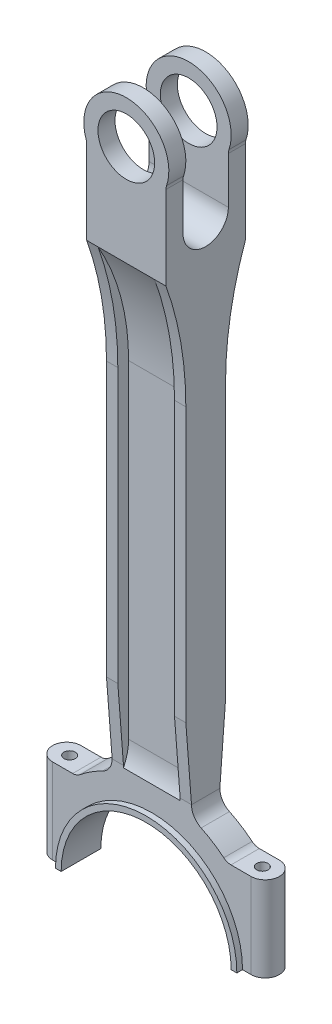
SolidWorks part; units mm, degrees
ref_plane "Front Plane" through (0, 0, 0) normal (0, 0, 1) x (1, 0, 0)
ref_plane "Top Plane" through (0, 0, 0) normal (0, 1, 0) x (1, 0, 0)
ref_plane "Right Plane" through (0, 0, 0) normal (1, 0, 0) x (0, 0, -1)
sketch "Sketch1" plane through (0, 0, 0) normal (0, 0, 1) x (1, 0, 0)
  line L0 (7, 27.7281) -> (7, -70.8443)
  line L1 (-7, 27.7281) -> (-7, -70.8443)
  line L2 (-20, -89.5793) -> (-15, -89.5793)
  line L3 (15, -89.5793) -> (20, -89.5793)
  line L4 (-20, -89.5793) -> (-20, -74.5793)
  line L5 (-20, -74.5793) -> (-13.9642, -74.5793)
  line L6 (13.9642, -74.5793) -> (20, -74.5793)
  line L7 (20, -74.5793) -> (20, -89.5793)
  circle A0 centre (0, 30.4207) radius 5
  arc A1 (7, 27.7281) -> (-7, 27.7281) centre (0, 30.4207) ccw
  arc A2 (-7, -70.8443) -> (-12.6948, -74.1248) centre (0, -89.5793) ccw
  arc A3 (15, -89.5793) -> (-15, -89.5793) centre (0, -89.5793) ccw
  arc A4 (12.6948, -74.1248) -> (7, -70.8443) centre (0, -89.5793) ccw
  arc A5 (-13.9642, -74.5793) -> (-12.6948, -74.1248) centre (-13.9642, -72.5793) ccw
  arc A6 (13.9642, -74.5793) -> (12.6948, -74.1248) centre (13.9642, -72.5793) cw
  point P18 (-13.2288, -74.5793)
  dimension "D1" = 10
  dimension "D2" = 15
  dimension "D4" = 30
  dimension "D5" = 40
  dimension "D9" = 2
  dimension "D3" = 120
  dimension "D6" = 7.5
  dimension "D7" = 7
  dimension "D8" = 7
  dimension "D10" = 5
extrude "Boss-Extrude1" add sketch "Sketch1" along normal blind 14
sketch "Sketch2" plane through (7, 0, 0) normal (1, 0, 0) x (0, 0, -1)
  line L0 (-11, 19.1557) -> (-11, 94.0269)
  line L2 (-11, 94.0269) -> (-3, 94.0269)
  line L3 (-3, 19.1557) -> (-3, 94.0269)
  line L4 (-14, -70.8443) -> (-14, 27.7281) construction
  arc A0 (-11, 19.1557) -> (-3, 19.1557) centre (-7, 19.1557) ccw
  dimension "D1" = 8
  dimension "D2" = 3
  dimension "D3" = 90
extrude "Cut-Extrude1" cut sketch "Sketch2" against normal blind 21 and the other way blind 14
sketch "Sketch3" plane through (-7, 0, 0) normal (-1, 0, 0) x (0, 0, 1)
  line L0 (14, 27.7281) -> (14, -70.8443) construction
  line L1 (0, 27.7281) -> (0, -70.8443) construction
  line L2 (3.5, -7.5793) -> (3.5, -89.5793)
  line L3 (14, -89.5793) -> (0, -89.5793) construction
  line L4 (10.5, -7.5793) -> (10.5, -89.5793)
  line L5 (0, 12.6135) -> (0, -89.5793)
  line L6 (14, 12.6135) -> (14, -89.5793)
  line L7 (14, -89.5793) -> (10.5, -89.5793)
  line L8 (0, -89.5793) -> (3.5, -89.5793)
  arc A0 (14, 12.6135) -> (10.5, -7.5793) centre (70.5, -7.5793) ccw
  arc A1 (0, 12.6135) -> (3.5, -7.5793) centre (-56.5, -7.5793) cw
  dimension "D1" = 60
  dimension "D2" = 60
  dimension "D3" = 82
  dimension "D4" = 60
  dimension "D5" = 3.5
  dimension "D6" = 3.5
  dimension "D7" = 82
extrude "Cut-Extrude2" cut sketch "Sketch3" against normal blind 28 and the other way blind 26
sketch "Sketch4" plane through (0, 0, 0) normal (1, 0, 0) x (0, 0, -1)
  line L0 (-5.4, -7.4574) -> (-5.4, -65.3135)
  line L1 (-3.5, -70.8443) -> (19.6376, -70.8443)
  line L2 (19.6376, -70.8443) -> (19.6376, 12.6135)
  line L3 (19.6376, 12.6135) -> (0, 12.6135)
  line L4 (-8.6, -7.4574) -> (-8.6, -65.3135)
  line L9 (-14, 12.6135) -> (-24.5306, 12.6135)
  line L10 (-24.5306, 12.6135) -> (-24.5306, -70.8443)
  line L12 (-24.5306, -70.8443) -> (-10.5, -70.8443)
  arc A0 (0, 12.6135) -> (-5.4, -7.4574) centre (34.6, -7.4574) ccw
  arc A1 (-5.4, -65.3135) -> (-3.5, -70.8443) centre (3.6, -65.3135) ccw
  arc A2 (-8.6, -7.4574) -> (-14, 12.6135) centre (-48.6, -7.4574) ccw
  arc A3 (-10.5, -70.8443) -> (-8.6, -65.3135) centre (-17.6, -65.3135) ccw
  dimension "D1" = 80
  dimension "D5" = 80
  dimension "D2" = 34.6
  dimension "D3" = 9
  dimension "D4" = 34.6
extrude "Cut-Extrude3" cut sketch "Sketch4" against normal blind 5 and the other way blind 5
sketch "Sketch5" plane through (0, 0, 10.5) normal (0, 0, 1) x (1, 0, 0)
  line L0 (-16, -89.5793) -> (-20, -89.5793)
  line L1 (-20, -89.5793) -> (-20, -74.5793)
  line L2 (-20, -74.5793) -> (-13.9642, -74.5793)
  line L3 (16, -89.5793) -> (20, -89.5793)
  line L4 (20, -89.5793) -> (20, -74.5793)
  line L5 (20, -74.5793) -> (13.9642, -74.5793)
  arc A0 (16, -89.5793) -> (-16, -89.5793) centre (0, -89.5793) ccw
  arc A1 (12.6948, -74.1248) -> (-12.6948, -74.1248) centre (0, -89.5793) ccw
  arc A3 (-13.9642, -74.5793) -> (-12.6948, -74.1248) centre (-13.9642, -72.5793) ccw
  arc A4 (13.9642, -74.5793) -> (12.6948, -74.1248) centre (13.9642, -72.5793) cw
  dimension "D1" = 16
  dimension "D2" = 2
  dimension "D3" = 20
extrude "Cut-Extrude4" cut sketch "Sketch5" against normal blind 1 from surface starting at face at (0, -61.296, 10.5)
sketch "Sketch6" plane through (7, 0, 0) normal (1, 0, 0) x (0, 0, -1)
  line L17 (-9.5, -70.8443) -> (-10.5, -70.8443)
  line L21 (-10.5, -70.8443) -> (-10.5, -55.8443)
  line L28 (-10.5, -70.8443) -> (-10.5, -7.5793) construction
  line L29 (-10.5, -55.8443) -> (-9.5, -70.8443)
  dimension "D1" = 1
  dimension "D2" = 15
extrude "Cut-Extrude6" cut sketch "Sketch5<3>" along normal blind 1 from surface starting at face at (0, -61.296, 3.5)
sketch "Sketch5<3>" plane through (0, 0, 10.5) normal (0, 0, 1) x (1, 0, 0) same geometry as "Sketch5"
sketch "Sketch8" plane through (0, -74.5793, 0) normal (0, 1, 0) x (1, 0, 0)
  line L0 (-20, -9.5) -> (-20, -4.5) construction
  line L1 (20, -9.5) -> (20, -4.5) construction
  line L2 (13.9642, -4.5) -> (20, -4.5) construction
  line L3 (-20, -4.5) -> (-13.9642, -4.5) construction
  circle A0 centre (17, -7) radius 1
  circle A1 centre (-17, -7) radius 1
  dimension "D1" = 2
  dimension "D2" = 2
  dimension "D3" = 3
  dimension "D4" = 3
  dimension "D5" = 2.5
  dimension "D6" = 2.5
extrude "Cut-Extrude8" cut sketch "Sketch8" against normal blind 15
fillet "Fillet2" 2 edges at (-20, -82.0793, 4.5) (-20, -82.0793, 9.5) type full round first side face at (0, -77.4214, 4.5) second side face at (0, -77.4214, 9.5) middle face at (-20, -82.0793, 7)
fillet "Fillet3" 2 edges at (20, -82.0793, 4.5) (20, -82.0793, 9.5) type full round first side face at (0.4167, -77.4214, 4.5) second side face at (0.4167, -77.4214, 9.5) middle face at (20, -82.0793, 7)
fillet "Fillet4" radius 3 2 edges at (-7, -70.8443, 7) (7, -70.8443, 7)
fillet "Fillet5" radius 2 4 edges at (-7, 27.7281, 1.5) (-7, 27.7281, 12.5) (7, 27.7281, 12.5) (7, 27.7281, 1.5)
sketch "Sketch10" plane through (7, 0, 0) normal (1, 0, 0) x (0, 0, -1)
  line L2 (-3.5, -55.8443) -> (-4.5, -68.867)
  line L6 (-4.5, -70.8443) -> (-3.5, -70.8443)
  line L7 (-3.5, -70.8443) -> (-3.5, -55.8443)
  line L8 (-3.5, -7.5793) -> (-3.5, -70.8443) construction
  line L11 (-4.5, -68.867) -> (-4.5, -70.8443) construction
  line L13 (-4.5, -68.867) -> (-4.5, -70.8443)
  dimension "D1" = 15
extrude "Cut-Extrude9" cut sketch "Sketch10" against normal blind 22 and the other way through all
sketch "Sketch11" plane through (7, 0, 0) normal (1, 0, 0) x (0, 0, -1)
  line L0 (-9.5, -70.8443) -> (-10.5, -70.8443)
  line L1 (-10.5, -70.8443) -> (-10.5, -55.8443)
  line L2 (-10.5, -70.8443) -> (-10.5, -7.5793) construction
  line L3 (-10.5, -55.8443) -> (-9.5, -68.867)
  line L4 (-9.5, -68.867) -> (-9.5, -70.8443)
extrude "Cut-Extrude10" cut sketch "Sketch11" against normal blind 19
